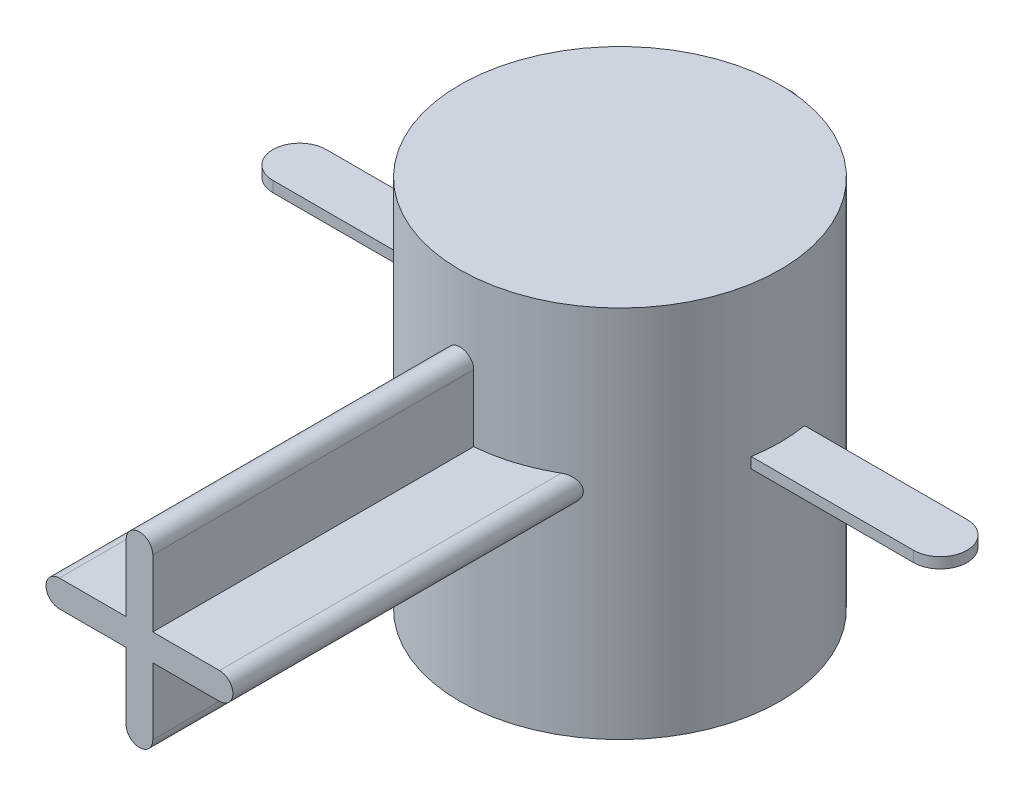
SolidWorks part; units mm, degrees
ref_plane "Front Plane" through (0, 0, 0) normal (0, 0, 1) x (1, 0, 0)
ref_plane "Top Plane" through (0, 0, 0) normal (0, 1, 0) x (1, 0, 0)
ref_plane "Right Plane" through (0, 0, 0) normal (1, 0, 0) x (0, 0, -1)
sketch "Sketch1" plane through (0, 0, 0) normal (0, 1, 0) x (1, 0, 0)
  circle A0 centre (0, 0) radius 38.1
  point P2 (0, 0)
  dimension "D1" = 76.2
extrude "Boss-Extrude1" add sketch "Sketch1" along normal blind 88.9 contours A0
ref_plane "Plane1" through (0, 50.8, 0) normal (0, 1, 0) x (1, 0, 0)
sketch "Sketch3" plane through (0, 50.8, 0) normal (0, 1, 0) x (1, 0, 0)
  line L0 (-76.2, 0) -> (76.2, 0) construction
  line L1 (-76.2, 6.35) -> (76.2, 6.35)
  line L2 (-76.2, -6.35) -> (76.2, -6.35)
  arc A0 (-76.2, 6.35) -> (-76.2, -6.35) centre (-76.2, 0) ccw
  arc A1 (76.2, -6.35) -> (76.2, 6.35) centre (76.2, 0) ccw
  point P3 (0, 0)
  point P8 (0, 0)
  point P9 (0, 0)
  point P10 (0, 0)
  point P11 (0, 0)
  dimension "D1" = 12.7
  dimension "D2" = 152.4
extrude "Boss-Extrude2" add sketch "Sketch3" along normal blind 2.54
ref_plane "Plane2" through (0, 0, 38.1) normal (0, 0, 1) x (1, 0, 0)
sketch "Sketch5" plane through (0, 0, 38.1) normal (0, 0, 1) x (1, 0, 0)
  line L0 (-19.05, 50.8) -> (19.05, 50.8) construction
  line L1 (-19.05, 53.975) -> (-3.175, 53.975)
  line L2 (-19.05, 47.625) -> (-3.175, 47.625)
  line L3 (0, 69.85) -> (0, 31.75) construction
  line L4 (3.175, 69.85) -> (3.175, 53.975)
  line L5 (-3.175, 69.85) -> (-3.175, 53.975)
  line L6 (3.175, 53.975) -> (19.05, 53.975)
  line L7 (-3.175, 47.625) -> (-3.175, 31.75)
  line L8 (3.175, 47.625) -> (3.175, 31.75)
  line L9 (3.175, 47.625) -> (19.05, 47.625)
  line L10 (37.5671, 50.8) -> (-37.5671, 50.8) construction
  arc A0 (-19.05, 53.975) -> (-19.05, 47.625) centre (-19.05, 50.8) ccw
  arc A1 (19.05, 47.625) -> (19.05, 53.975) centre (19.05, 50.8) ccw
  arc A2 (3.175, 69.85) -> (-3.175, 69.85) centre (0, 69.85) ccw
  arc A3 (-3.175, 31.75) -> (3.175, 31.75) centre (0, 31.75) ccw
  point P2 (0, 0)
  point P17 (0, 50.8)
  point P21 (0, 50.8)
  point P22 (0, 0)
  dimension "D1" = 38.1
  dimension "D2" = 38.1
  dimension "D3" = 6.35
  dimension "D4" = 19.05
  dimension "D5" = 19.05
  dimension "D6" = 6.35
extrude "Boss-Extrude4" add sketch "Sketch5" against normal up to surface and the other way blind 76.2 separate body up to face at (37.8336, 52.07, 0)
sketch "Sketch6" plane through (0, 88.9, 0) normal (0, 1, 0) x (1, 0, 0)
  line L0 (0, 0) -> (0, 38.1) construction
  line L1 (0, 0) -> (38.1, 0) construction
  circle A0 centre (0, 0) radius 38.1 construction
  arc A1 (37.5671, -6.35) -> (37.5671, 6.35) centre (0, 0) ccw construction
  dimension "D1" = 90
ref_plane "Plane3" through (0, 88.9, -38.1) normal (0, 0, -1) x (-1, 0, 0)
sketch "Sketch7" plane through (0, 88.9, -38.1) normal (0, 0, -1) x (-1, 0, 0)
  line L0 (38.1, 0) -> (-38.1, 0) construction
  circle A0 centre (0, -7.62) radius 5.08
  circle A1 centre (0, -7.62) radius 3.175
  point P5 (0, 0)
  point P6 (0, 0)
  dimension "D2" = 6.35
  dimension "D3" = 10.16
  dimension "D1" = 7.62
extrude "Boss-Extrude7" add sketch "Sketch7" against normal up to surface and the other way blind 2.54 up to face at (37.8336, 52.07, 0)
